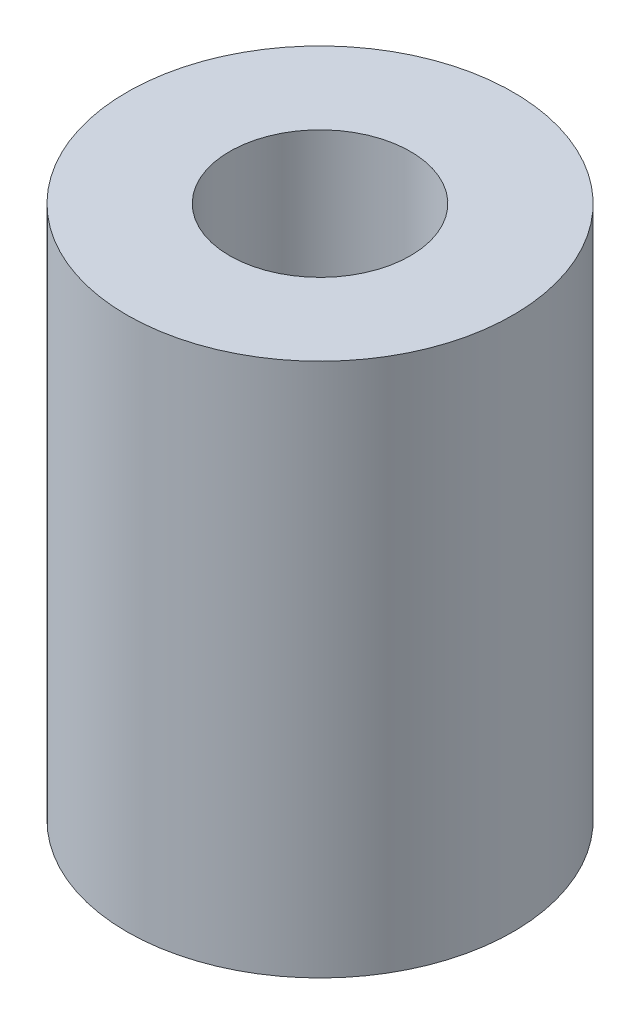
SolidWorks part; units mm, degrees
material "PET"
ref_plane "Front" through (0, 0, 0) normal (0, 0, 1) x (1, 0, 0)
ref_plane "Top" through (0, 0, 0) normal (0, 1, 0) x (1, 0, 0)
ref_plane "Right" through (0, 0, 0) normal (1, 0, 0) x (0, 0, -1)
sketch "Sketch1" plane through (0, 0, 0) normal (0, 1, 0) x (1, 0, 0)
  circle A0 centre (0, 0) radius 2.794
  circle A1 centre (0, 0) radius 5.969
  dimension "D1" = 3.175
  dimension "D2" = 5.588
extrude "Boss-Extrude1" add sketch "Sketch1" along normal blind 16.51
